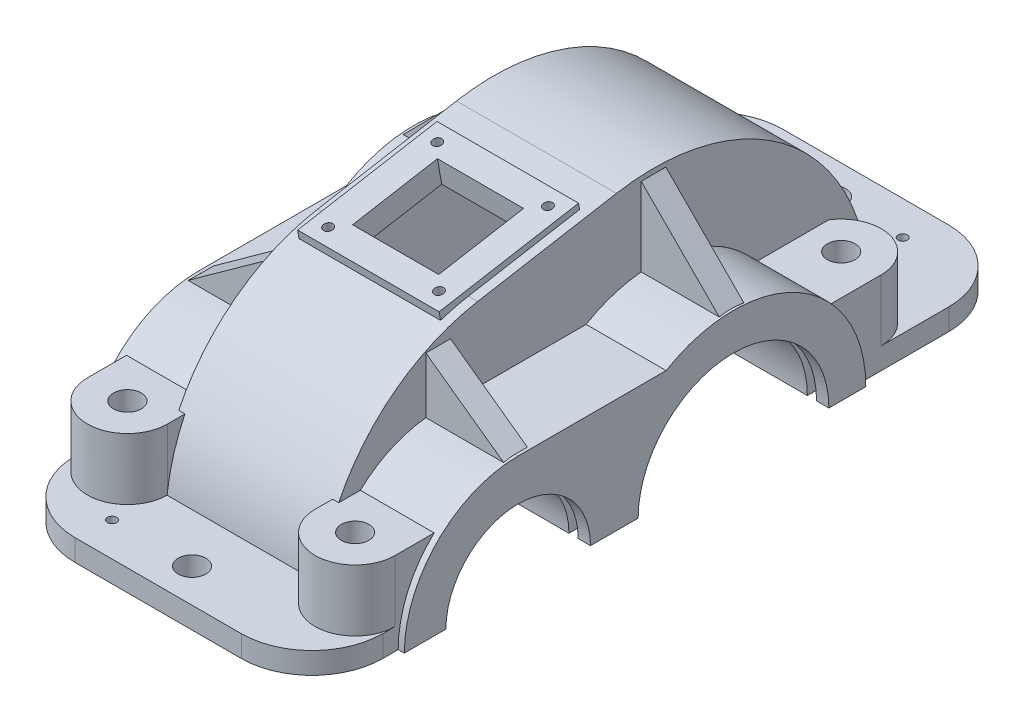
SolidWorks part; units mm, degrees
ref_plane "前视基准面" through (0, 0, 0) normal (0, 0, 1) x (1, 0, 0)
ref_plane "上视基准面" through (0, 0, 0) normal (0, 1, 0) x (1, 0, 0)
ref_plane "右视基准面" through (0, 0, 0) normal (1, 0, 0) x (0, 0, -1)
sketch "草图1" plane through (0, 0, 0) normal (0, 1, 0) x (1, 0, 0)
  line L1 (-27, 115) -> (27, 115)
  line L2 (-50, 92) -> (-50, -92)
  line L3 (-27, -115) -> (27, -115)
  line L4 (50, 92) -> (50, -92)
  line L5 (-50, 115) -> (50, -115) construction
  line L6 (-50, -115) -> (50, 115) construction
  arc A0 (27, 115) -> (50, 92) centre (27, 92) cw
  arc A1 (-27, 115) -> (-50, 92) centre (-27, 92) ccw
  arc A2 (27, -115) -> (50, -92) centre (27, -92) ccw
  arc A3 (-50, -92) -> (-27, -115) centre (-27, -92) ccw
  point P0 (0, 0)
  dimension "D3" = 23
  dimension "D1" = 100
  dimension "D2" = 230
extrude "凸台-拉伸1" add sketch "草图1" along normal blind 7
sketch "草图2" plane through (0, 0, 0) normal (1, 0, 0) x (0, 0, -1)
  line L0 (-92, 0) -> (92, 0) construction
  line L1 (-115, 7) -> (-115, 0) construction
  line L2 (-50, 37) -> (-1.9089, 37)
  line L5 (-92, 0) -> (92, 0)
  circle A0 centre (-50, 0) radius 37
  circle A1 centre (20, 0) radius 43
  dimension "D1" = 74
  dimension "D2" = 86
  dimension "D3" = 70
  dimension "D4" = 65
extrude "凸台-拉伸2" add sketch "草图2" along normal mid plane 104 contours A1 A0 | A1 A0 | A1 L2 A0 | A0 A1 region at (0, 31.8756, 20.6869) region at (0, 16.2455, 52.0603) region at (0, 18.7643, -21.7895) region at (0, 7.3014, 18.0775)
sketch "草图3" plane through (0, 0, 0) normal (1, 0, 0) x (0, 0, -1)
  line L0 (-37.1667, 61.0755) -> (7.957, 68.9563)
  line L1 (-86.3318, 7) -> (-22.4264, 7) construction
  line L2 (-86.3318, 7) -> (-22.4264, 7)
  line L3 (-92, 7) -> (-86.3318, 7) construction
  line L4 (-92, 7) -> (-86.3318, 7)
  line L5 (-22.4264, 7) -> (92.0719, 7)
  circle A0 centre (-50, 0) radius 23.5
  circle A1 centre (20, 0) radius 70
  circle A2 centre (-26.5, 0) radius 62
  dimension "D1" = 47
  dimension "D2" = 140
  dimension "D3" = 124
extrude "凸台-拉伸4" add sketch "草图3" along normal mid plane 52 contours A2 L5 A1 | A1 A2 L4 L2 A0 | L5 A2 A1 A0 L2 | A0 A1 L2 | A1 A0 L2 | A2 A1 L0 region at (0, 63.7485, 14.7428) region at (0, 36.5136, 56.8246) region at (0, 38.2846, -45.7222) region at (0, 29.5675, 5.3797) region at (0, 14.256, 57.9954) region at (0, 13.3434, 40.0072)
sketch "草图4" plane through (0, 7, 0) normal (0, 1, 0) x (1, 0, 0)
  line L0 (-27, -115) -> (27, -115) construction
  line L1 (50, -92) -> (50, -86.3318) construction
  line L3 (50, -88) -> (24, -88)
  line L4 (50, -88) -> (50, -50)
  line L5 (50, -50) -> (24, -50)
  line L6 (24, -88) -> (24, -50)
  line L7 (52, -50) -> (26, -50) construction
  line L8 (0, -115) -> (0, -61.8107) construction
  line L9 (-24, -88) -> (-24, -50)
  line L10 (-50, -50) -> (-24, -50)
  line L11 (-50, -88) -> (-50, -50)
  line L12 (-50, -88) -> (-24, -88)
  line L13 (50, 62.4264) -> (50, 92) construction
  line L14 (0, 0) -> (0, 97.4407) construction
  line L15 (50, 70) -> (24, 70)
  line L16 (50, 70) -> (50, 25)
  line L17 (50, 25) -> (24, 25)
  line L18 (24, 70) -> (24, 25)
  line L19 (-24, 70) -> (-24, 25)
  line L20 (-50, 25) -> (-24, 25)
  line L21 (-50, 70) -> (-50, 25)
  line L22 (-50, 70) -> (-24, 70)
  circle A0 centre (37, -88) radius 13
  circle A1 centre (-37, -88) radius 13
  circle A2 centre (37, 70) radius 13
  circle A3 centre (-37, 70) radius 13
  dimension "D1" = 27
  dimension "D2" = 37
  dimension "D3" = 158
  dimension "D4" = 45
extrude "凸台-拉伸5" add sketch "草图4" along normal blind 20 contours L22 L19 L20 L21 | A3 | A2 | L15 L18 L17 L16 | L5 L6 L3 L4 | A0 | L10 L9 L12 L11 | A1
ref_plane "基准面1" through (0, 0, 50) normal (0, 0, 1) x (1, 0, 0)
sketch "草图5" plane through (0, 0, 50) normal (0, 0, 1) x (1, 0, 0)
  line L0 (51, 37) -> (26, 55)
  line L1 (26, 27) -> (26, 61.0755) construction
  line L2 (52, 37) -> (26, 37) construction
  line L3 (52, 0) -> (52, 37) construction
  dimension "D1" = 55
  dimension "D2" = 1
rib "筋5" sketch "草图5" sketch "草图5" thickness 8 extrusion direction parallel to sketch draft on no parameters "D1"=8
mirror "镜向1" about plane through (0, 0, 0) normal (1, 0, 0) of "筋5"
ref_plane "基准面2" through (0, 0, -20) normal (0, 0, 1) x (1, 0, 0)
sketch "草图6" plane through (0, 0, -20) normal (0, 0, 1) x (1, 0, 0)
  line L0 (51.181, 43) -> (26, 68.3184)
  line L1 (26, 61.0755) -> (26, 68.9563) construction
  line L2 (52, 43) -> (26, 43) construction
  dimension "D1" = 51.181
  dimension "D2" = 68.3184
rib "筋6" sketch "草图6" sketch "草图6" thickness 8 extrusion direction parallel to sketch draft on no parameters "D1"=8
mirror "镜向2" about plane through (0, 0, 0) normal (1, 0, 0) of "筋6"
sketch "草图7" plane through (0, 7, 0) normal (0, 1, 0) x (1, 0, 0)
  line L0 (0, -115) -> (0, 115) construction
  line L1 (-27, -115) -> (27, -115) construction
  line L2 (27, 115) -> (-27, 115) construction
  circle A0 centre (0, 104) radius 4.5
  circle A1 centre (0, -104) radius 4.5
  arc A2 (50, 70) -> (26, 76.9282) centre (37, 70) ccw construction
  dimension "D1" = 9
  dimension "D2" = 11
  dimension "D3" = 34
  dimension "D4" = 9
extrude "切除-拉伸1" cut sketch "草图7" against normal up to next
sketch "草图8" plane through (0, 27, 0) normal (0, 1, 0) x (1, 0, 0)
  circle A0 centre (-37, 70) radius 4.5
  dimension "D1" = 9
extrude "切除-拉伸2" cut sketch "草图8" against normal up to next
pattern_linear "阵列(线性)1" count 2 spacing 74 along (1, 0, 0) count 2 spacing 158 along (0, 0, 1) of "切除-拉伸2"
sketch "草图9" plane through (0, 7, 0) normal (0, 1, 0) x (1, 0, 0)
  line L0 (-3, -104) -> (-26, -104) construction
  circle A0 centre (-26, -104) radius 1.5
  dimension "D2" = 3
  dimension "D1" = 23
extrude "切除-拉伸3" cut sketch "草图9" against normal up to next
sketch "草图10" plane through (0, 7, 0) normal (0, 1, 0) x (1, 0, 0)
  line L0 (0, 104) -> (23, 104) construction
  circle A0 centre (23, 104) radius 1.5
  dimension "D2" = 3
  dimension "D1" = 23
extrude "切除-拉伸4" cut sketch "草图10" against normal up to next
sketch "草图11" plane through (0, 0, 0) normal (1, 0, 0) x (0, 0, -1)
  circle A0 centre (-50, 0) radius 23.5
  circle A1 centre (20, 0) radius 31
  dimension "D1" = 47
  dimension "D2" = 62
extrude "切除-拉伸5" cut sketch "草图11" against normal mid plane 571
sketch "草图13" plane through (0, 0, 0) normal (1, 0, 0) x (0, 0, -1)
  circle A0 centre (-50, 0) radius 27.5
  circle A1 centre (20, 0) radius 35
  dimension "D1" = 70
  dimension "D2" = 55
extrude "切除-拉伸6" cut sketch "草图13" against normal blind 3 from offset 48
mirror "镜向3" about plane through (0, 0, 0) normal (1, 0, 0) of "切除-拉伸6"
sketch "草图15" plane through (0, 0, 0) normal (1, 0, 0) x (0, 0, -1)
  line L1 (-82.5, 0) -> (84, 0)
  line L2 (8.9892, 63.0457) -> (-36.1344, 55.165)
  line L3 (8.9892, 63.0457) -> (-36.1344, 55.165)
  line L4 (63, 0) -> (92, 0) construction
  arc A4 (83.6792, 6.4) -> (8.9892, 63.0457) centre (20, 0) ccw
  arc A5 (-36.1344, 55.165) -> (-76.911, 24.3871) centre (-26.5, 0) ccw
  arc A6 (84, 0) -> (8.9892, 63.0457) centre (20, 0) ccw
  arc A7 (-36.1344, 55.165) -> (-82.5, 0) centre (-26.5, 0) ccw
  dimension "D1" = 6
extrude "切除-拉伸7" cut sketch "草图15" against normal mid plane 40
sketch "草图16" plane through (0, 0, 0) normal (1, 0, 0) x (0, 0, -1)
  line L0 (20, 0) -> (20, 98.9818) construction
  line L1 (20, 0) -> (2.1762, 101.0838) construction
  line L2 (7.4973, 70.9063) -> (-24.0255, 65.4009) construction
  line L5 (-24.0255, 65.4009) -> (-23.1653, 60.4754) construction
  line L6 (-46.6826, 61.4439) -> (-45.8224, 56.5184)
  line L7 (-1.3685, 69.3579) -> (-0.5083, 64.4324)
  line L8 (-46.6826, 61.4439) -> (-1.3685, 69.3579)
  line L9 (-45.8224, 56.5184) -> (-0.5083, 64.4324)
  line L11 (-37.1667, 61.0755) -> (7.957, 68.9563) construction
  dimension "D1" = 10
  dimension "D2" = 32
  dimension "D5" = 5
  dimension "D6" = 2
  dimension "D3" = 23
  dimension "D4" = 23
extrude "凸台-拉伸6" add sketch "草图16" along normal mid plane 46
sketch "草图17" plane through (0, 67.5369, 11.7951) normal (0, 0.9851, 0.172) x (1, 0, 0)
  line L0 (0, -35.4155) -> (0, 10.5845) construction
  line L1 (23, -35.4155) -> (-23, -35.4155) construction
  line L2 (23, 10.5845) -> (-23, 10.5845) construction
  line L4 (-14, -26.4155) -> (14, -26.4155)
  line L5 (-14, -26.4155) -> (-14, 1.5845)
  line L6 (-14, 1.5845) -> (14, 1.5845)
  line L7 (14, -26.4155) -> (14, 1.5845)
  line L8 (-14, -26.4155) -> (14, 1.5845) construction
  line L9 (-14, 1.5845) -> (14, -26.4155) construction
  point P6 (0, -12.4155)
  dimension "D1" = 28
  dimension "D2" = 28
extrude "切除-拉伸8" cut sketch "草图17" against normal up to next
sketch "草图18" plane through (0, 67.5369, 11.7951) normal (0, 0.9851, 0.172) x (1, 0, 0)
  line L0 (0, -26.4155) -> (0, 1.5845) construction
  line L1 (-14, -26.4155) -> (14, -26.4155) construction
  line L2 (14, 1.5845) -> (-14, 1.5845) construction
  line L4 (-18, -30.4155) -> (18, -30.4155) construction
  line L5 (-18, -30.4155) -> (-18, 5.5845) construction
  line L6 (-18, 5.5845) -> (18, 5.5845) construction
  line L7 (18, -30.4155) -> (18, 5.5845) construction
  line L8 (-18, -30.4155) -> (18, 5.5845) construction
  line L9 (-18, 5.5845) -> (18, -30.4155) construction
  circle A0 centre (-18, -30.4155) radius 1.5
  circle A1 centre (18, -30.4155) radius 1.5
  circle A2 centre (-18, 5.5845) radius 1.5
  circle A3 centre (18, 5.5845) radius 1.5
  point P6 (0, -12.4155)
  dimension "D3" = 3
  dimension "D4" = 3
  dimension "D1" = 36
  dimension "D2" = 36
extrude "切除-拉伸9" cut sketch "草图18" against normal up to next
